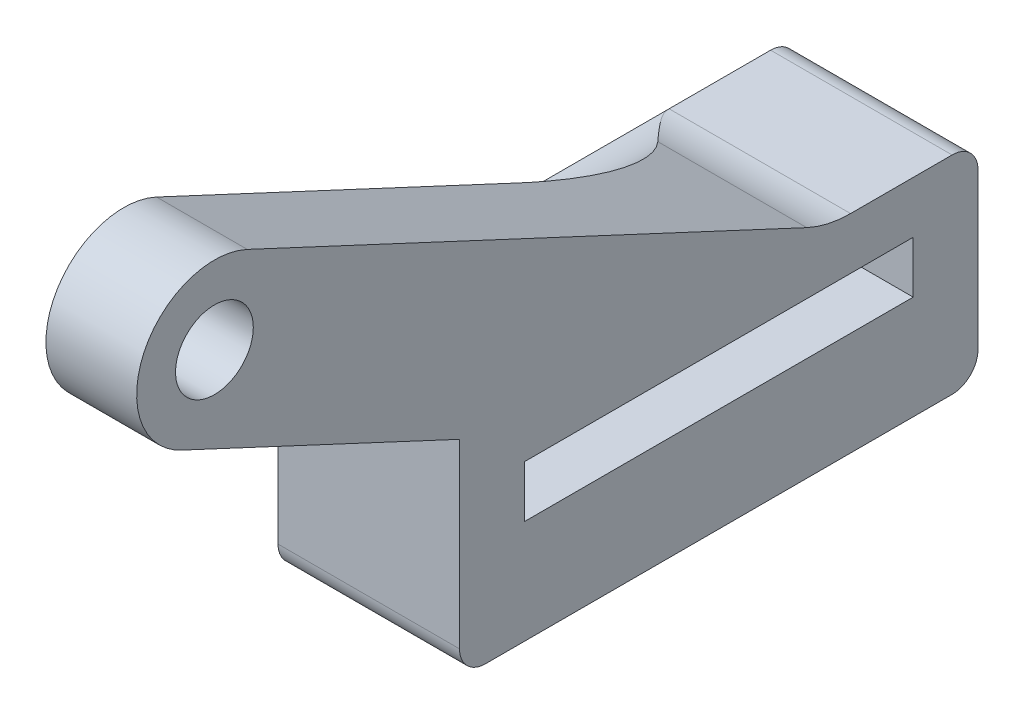
SolidWorks part; units mm, degrees
ref_plane "Alzado" through (0, 0, 0) normal (0, 0, 1) x (1, 0, 0)
ref_plane "Planta" through (0, 0, 0) normal (0, 1, 0) x (1, 0, 0)
ref_plane "Vista lateral" through (0, 0, 0) normal (1, 0, 0) x (0, 0, -1)
sketch "Croquis1" plane through (0, 0, 0) normal (1, 0, 0) x (0, 0, -1)
  line L0 (4.1972, 4) -> (-18.1868, 14.4378)
  line L1 (4.1972, 4) -> (10, 4)
  line L2 (-10, 4) -> (-10, -4)
  line L3 (-10, -4) -> (10, -4)
  line L4 (10, 4) -> (10, -4)
  line L5 (-10, 4) -> (10, -4) construction
  line L6 (-10, -4) -> (10, 4) construction
  line L7 (-7.5, 2) -> (7.5, 2)
  line L8 (-7.5, 2) -> (-7.5, 0)
  line L9 (-7.5, 0) -> (7.5, 0)
  line L10 (7.5, 2) -> (7.5, 0)
  line L11 (-7.5, 2) -> (7.5, 0) construction
  line L12 (-7.5, 0) -> (7.5, 2) construction
  line L13 (-10, 4) -> (-20.7225, 9)
  line L14 (-18.1868, 14.4378) -> (-20.7225, 9) construction
  line L15 (-10, 4) -> (4.1972, 4) construction
  arc A0 (-18.1868, 14.4378) -> (-20.7225, 9) centre (-19.4547, 11.7189) ccw
  circle A1 centre (-19.4547, 11.7189) radius 1.5
  point P0 (0, 0)
  point P6 (0, 1)
  dimension "D9" = 3
  dimension "D1" = 8
  dimension "D2" = 20
  dimension "D3" = 2
  dimension "D4" = 15
  dimension "D5" = 2
  dimension "D6" = 6
  dimension "D7" = 25
  dimension "D8" = 5
extrude "Saliente-Extruir1" add sketch "Croquis1" along normal mid plane 7
sketch "Croquis2" plane through (-3.5, 0, 0) normal (-1, 0, 0) x (0, 0, 1)
  line L0 (-4.1972, 4) -> (10, 4)
  line L6 (-10, 4) -> (-10, -4)
  line L7 (-10, -4) -> (10, -4)
  line L8 (10, -4) -> (10, 4)
  line L9 (10, 4) -> (20.7225, 9)
  line L10 (18.1868, 14.4378) -> (-4.1972, 4)
  line L11 (-4.1972, 4) -> (-10, 4)
  line L15 (10, 4) -> (20.7225, 9)
  line L16 (18.1868, 14.4378) -> (-4.1972, 4)
  arc A1 (20.7225, 9) -> (18.1868, 14.4378) centre (19.4547, 11.7189) ccw
  arc A2 (20.7225, 9) -> (18.1868, 14.4378) centre (19.4547, 11.7189) ccw
  dimension "D1" = 0
extrude "Cortar-Extruir1" cut sketch "Croquis2" against normal up to surface (3.5 mm away)
fillet "Redondeo1" radius 4 2 edges at (0, 4, 2.9014) (1.75, 4, -4.1972)
fillet "Redondeo3" radius 1 3 edges at (0, 4, -10) (0, -4, -10) (0, -4, 10)
